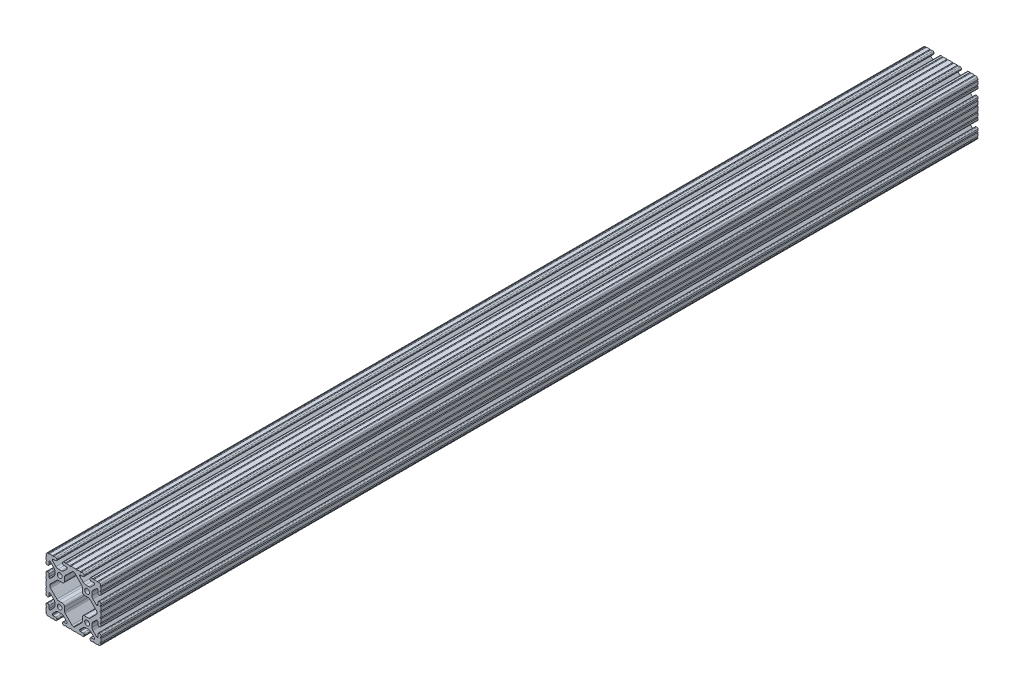
SolidWorks part; units mm, degrees
ref_plane "Front Plane" through (0, 0, 0) normal (0, 0, 1) x (1, 0, 0)
ref_plane "Top Plane" through (0, 0, 0) normal (0, 1, 0) x (1, 0, 0)
ref_plane "Right Plane" through (0, 0, 0) normal (1, 0, 0) x (0, 0, -1)
sketch "Sketch1" plane through (0, 0, 0) normal (0, 0, 1) x (1, 0, 0)
  line L0 (0, 38.1) -> (0, -38.1) construction
  line L1 (-38.1, -38.1) -> (38.1, -38.1) construction
  line L2 (-38.1, -38.1) -> (-38.1, 38.1) construction
  line L3 (-38.1, 38.1) -> (38.1, 38.1) construction
  line L4 (38.1, -38.1) -> (38.1, 38.1) construction
  line L5 (0, 38.1) -> (0, -38.1) construction
  line L6 (-38.1, 0) -> (38.1, 0) construction
  line L7 (-19.05, 19.05) -> (19.05, 19.05) construction
  line L8 (-19.05, 19.05) -> (-19.05, -19.05) construction
  line L9 (-19.05, -19.05) -> (19.05, -19.05) construction
  line L10 (19.05, 19.05) -> (19.05, -19.05) construction
  line L11 (-23.114, 38.1) -> (-23.114, -38.1) construction
  line L12 (-23.114, -38.1) -> (-14.986, 38.1) construction
  line L13 (-14.986, 38.1) -> (-14.986, -38.1) construction
  circle A0 centre (19.05, 19.05) radius 3.3274
  point P0 (0, 0)
  point P9 (0, 0)
  point P12 (-19.05, 0)
  line B0 (-11.3637, -22.8433) -> (-2.0515, -32.1555)
  line B1 (-12.2936, -15.4686) -> (-12.2936, -20.5983)
  line B2 (-20.769, -12.2936) -> (-15.4686, -12.2936)
  line B3 (-31.9021, -2.4756) -> (-23.0141, -11.3637)
  line B4 (-23.0141, 11.3637) -> (-31.9021, 2.4756)
  line B5 (-15.4686, 12.2936) -> (-20.769, 12.2936)
  line B6 (-12.2936, 20.5983) -> (-12.2936, 15.4686)
  line B7 (-2.0515, 32.1555) -> (-11.3637, 22.8433)
  line B8 (11.3637, 22.8433) -> (2.0515, 32.1555)
  line B9 (12.2936, 15.4686) -> (12.2936, 20.5983)
  line B10 (20.769, 12.2936) -> (15.4686, 12.2936)
  line B11 (31.9021, 2.4756) -> (23.0141, 11.3637)
  line B12 (23.0141, -11.3637) -> (31.9021, -2.4756)
  line B13 (15.4686, -12.2936) -> (20.769, -12.2936)
  line B14 (12.2936, -20.5983) -> (12.2936, -15.4686)
  line B15 (2.0515, -32.1555) -> (11.3637, -22.8433)
  line B16 (-4.7773, 38.1) -> (-9.6053, 38.1)
  line B17 (-11.1289, 38.1) -> (-13.4112, 38.1)
  line B18 (-14.986, 36.5252) -> (-14.986, 35.6108)
  line B19 (-13.4112, 34.036) -> (-9.652, 34.036)
  line B20 (-8.763, 33.147) -> (-8.763, 32.4935)
  line B21 (-9.0234, 31.8649) -> (-13.6907, 27.1976)
  line B22 (-17.0493, 25.8064) -> (-21.0507, 25.8064)
  line B23 (-24.4093, 27.1976) -> (-29.1002, 31.8885)
  line B24 (-29.337, 32.7207) -> (-29.337, 33.147)
  line B25 (-28.448, 34.036) -> (-24.6888, 34.036)
  line B26 (-23.114, 35.6108) -> (-23.114, 36.5252)
  line B27 (-24.6888, 38.1) -> (-27.0772, 38.1)
  line B28 (-28.6011, 38.1) -> (-33.4288, 38.1)
  line B29 (-38.1, 33.373) -> (-38.1, 28.5453)
  line B30 (-38.1, 27.0238) -> (-38.1, 24.6302)
  line B31 (-36.5252, 23.0554) -> (-35.6108, 23.0554)
  line B32 (-34.036, 24.6302) -> (-34.036, 28.448)
  line B33 (-33.147, 29.337) -> (-32.6643, 29.337)
  line B34 (-32.0357, 29.0766) -> (-27.1976, 24.2385)
  line B35 (-25.8064, 20.8799) -> (-25.8064, 17.2201)
  line B36 (-27.1976, 13.8615) -> (-31.9489, 9.1101)
  line B37 (-32.7869, 8.763) -> (-33.0603, 8.763)
  line B38 (-34.036, 9.7387) -> (-34.036, 13.4698)
  line B39 (-35.6108, 15.0446) -> (-36.5252, 15.0446)
  line B40 (-38.1, 13.4698) -> (-38.1, 11.075)
  line B41 (-38.1, 9.552) -> (-38.1, 4.7238)
  line B42 (-38.1, 3.2007) -> (-38.1, -3.2007)
  line B43 (-38.1, -4.7238) -> (-38.1, -9.552)
  line B44 (-38.1, -11.075) -> (-38.1, -13.4698)
  line B45 (-36.5252, -15.0446) -> (-35.6108, -15.0446)
  line B46 (-34.036, -13.4698) -> (-34.036, -9.7387)
  line B47 (-33.0603, -8.763) -> (-32.7869, -8.763)
  line B48 (-31.9489, -9.1101) -> (-27.1976, -13.8615)
  line B49 (-25.8064, -17.2201) -> (-25.8064, -20.8799)
  line B50 (-27.1976, -24.2385) -> (-32.0357, -29.0766)
  line B51 (-32.6643, -29.337) -> (-33.147, -29.337)
  line B52 (-34.036, -28.448) -> (-34.036, -24.6302)
  line B53 (-35.6108, -23.0554) -> (-36.5252, -23.0554)
  line B54 (-38.1, -24.6302) -> (-38.1, -27.0238)
  line B55 (-38.1, -28.5453) -> (-38.1, -33.373)
  line B56 (-33.4288, -38.1) -> (-28.6011, -38.1)
  line B57 (-27.0772, -38.1) -> (-24.6888, -38.1)
  line B58 (-23.114, -36.5252) -> (-23.114, -35.6108)
  line B59 (-24.6888, -34.036) -> (-28.448, -34.036)
  line B60 (-29.337, -33.147) -> (-29.337, -32.7207)
  line B61 (-29.1002, -31.8885) -> (-24.4093, -27.1976)
  line B62 (-21.0507, -25.8064) -> (-17.0493, -25.8064)
  line B63 (-13.6907, -27.1976) -> (-9.0234, -31.8649)
  line B64 (-8.763, -32.4935) -> (-8.763, -33.147)
  line B65 (-9.652, -34.036) -> (-13.4112, -34.036)
  line B66 (-14.986, -35.6108) -> (-14.986, -36.5252)
  line B67 (-13.4112, -38.1) -> (-11.1289, -38.1)
  line B68 (-9.6053, -38.1) -> (-4.7773, -38.1)
  line B69 (-3.2537, -38.1) -> (3.2537, -38.1)
  line B70 (4.7773, -38.1) -> (9.6053, -38.1)
  line B71 (11.1289, -38.1) -> (13.4112, -38.1)
  line B72 (14.986, -36.5252) -> (14.986, -35.6108)
  line B73 (13.4112, -34.036) -> (9.652, -34.036)
  line B74 (8.763, -33.147) -> (8.763, -32.4935)
  line B75 (9.0234, -31.8649) -> (13.6907, -27.1976)
  line B76 (17.0493, -25.8064) -> (21.0507, -25.8064)
  line B77 (24.4093, -27.1976) -> (29.1002, -31.8885)
  line B78 (29.337, -32.7207) -> (29.337, -33.147)
  line B79 (28.448, -34.036) -> (24.6888, -34.036)
  line B80 (23.114, -35.6108) -> (23.114, -36.5252)
  line B81 (24.6888, -38.1) -> (27.0772, -38.1)
  line B82 (28.6011, -38.1) -> (33.4288, -38.1)
  line B83 (38.1, -33.373) -> (38.1, -28.5453)
  line B84 (38.1, -27.0238) -> (38.1, -24.6302)
  line B85 (36.5252, -23.0554) -> (35.6108, -23.0554)
  line B86 (34.036, -24.6302) -> (34.036, -28.448)
  line B87 (33.147, -29.337) -> (32.6643, -29.337)
  line B88 (32.0357, -29.0766) -> (27.1976, -24.2385)
  line B89 (25.8064, -20.8799) -> (25.8064, -17.2201)
  line B90 (27.1976, -13.8615) -> (31.9489, -9.1101)
  line B91 (32.7869, -8.763) -> (33.0603, -8.763)
  line B92 (34.036, -9.7387) -> (34.036, -13.4698)
  line B93 (35.6108, -15.0446) -> (36.5252, -15.0446)
  line B94 (38.1, -13.4698) -> (38.1, -11.075)
  line B95 (38.1, -9.552) -> (38.1, -4.7238)
  line B96 (38.1, -3.2007) -> (38.1, 3.2007)
  line B97 (38.1, 4.7238) -> (38.1, 9.552)
  line B98 (38.1, 11.075) -> (38.1, 13.4698)
  line B99 (36.5252, 15.0446) -> (35.6108, 15.0446)
  line B100 (34.036, 13.4698) -> (34.036, 9.7387)
  line B101 (33.0603, 8.763) -> (32.7869, 8.763)
  line B102 (31.9489, 9.1101) -> (27.1976, 13.8615)
  line B103 (25.8064, 17.2201) -> (25.8064, 20.8799)
  line B104 (27.1976, 24.2385) -> (32.0357, 29.0766)
  line B105 (32.6643, 29.337) -> (33.147, 29.337)
  line B106 (34.036, 28.448) -> (34.036, 24.6302)
  line B107 (35.6108, 23.0554) -> (36.5252, 23.0554)
  line B108 (38.1, 24.6302) -> (38.1, 27.0238)
  line B109 (38.1, 28.5453) -> (38.1, 33.373)
  line B110 (33.4288, 38.1) -> (28.6011, 38.1)
  line B111 (27.0772, 38.1) -> (24.6888, 38.1)
  line B112 (23.114, 36.5252) -> (23.114, 35.6108)
  line B113 (24.6888, 34.036) -> (28.448, 34.036)
  line B114 (29.337, 33.147) -> (29.337, 32.7207)
  line B115 (29.1002, 31.8885) -> (24.4093, 27.1976)
  line B116 (21.0507, 25.8064) -> (17.0493, 25.8064)
  line B117 (13.6907, 27.1976) -> (9.0234, 31.8649)
  line B118 (8.763, 32.4935) -> (8.763, 33.147)
  line B119 (9.652, 34.036) -> (13.4112, 34.036)
  line B120 (14.986, 35.6108) -> (14.986, 36.5252)
  line B121 (13.4112, 38.1) -> (11.1289, 38.1)
  line B122 (9.6053, 38.1) -> (4.7773, 38.1)
  line B123 (3.2537, 38.1) -> (-3.2537, 38.1)
  circle B124 centre (-19.05, 19.05) radius 3.3274
  circle B125 centre (-19.05, -19.05) radius 3.3274
  circle B126 centre (19.05, -19.05) radius 3.3274
  circle B127 centre (19.05, 19.05) radius 3.3274
  arc B128 (0, -33.011) -> (2.0515, -32.1555) centre (-0.0139, -30.09) ccw
  arc B129 (-2.0515, -32.1555) -> (0, -33.011) centre (0.0139, -30.09) ccw
  arc B130 (-12.2936, -20.5983) -> (-11.3637, -22.8433) centre (-9.1186, -20.5983) ccw
  arc B131 (-12.2936, -15.4686) -> (-15.4686, -12.2936) centre (-15.4686, -15.4686) ccw
  arc B132 (-23.0141, -11.3637) -> (-20.769, -12.2936) centre (-20.769, -9.1186) ccw
  arc B133 (-32.7287, 0) -> (-31.9021, -2.4756) centre (-29.8367, -0.4102) ccw
  arc B134 (-31.9021, 2.4756) -> (-32.7287, 0) centre (-29.8367, 0.4102) ccw
  arc B135 (-20.769, 12.2936) -> (-23.0141, 11.3637) centre (-20.769, 9.1186) ccw
  arc B136 (-15.4686, 12.2936) -> (-12.2936, 15.4686) centre (-15.4686, 15.4686) ccw
  arc B137 (-11.3637, 22.8433) -> (-12.2936, 20.5983) centre (-9.1186, 20.5983) ccw
  arc B138 (0, 33.011) -> (-2.0515, 32.1555) centre (0.0139, 30.09) ccw
  arc B139 (2.0515, 32.1555) -> (0, 33.011) centre (-0.0139, 30.09) ccw
  arc B140 (12.2936, 20.5983) -> (11.3637, 22.8433) centre (9.1186, 20.5983) ccw
  arc B141 (12.2936, 15.4686) -> (15.4686, 12.2936) centre (15.4686, 15.4686) ccw
  arc B142 (23.0141, 11.3637) -> (20.769, 12.2936) centre (20.769, 9.1186) ccw
  arc B143 (32.7287, 0) -> (31.9021, 2.4756) centre (29.8367, 0.4102) ccw
  arc B144 (31.9021, -2.4756) -> (32.7287, 0) centre (29.8367, -0.4102) ccw
  arc B145 (20.769, -12.2936) -> (23.0141, -11.3637) centre (20.769, -9.1186) ccw
  arc B146 (15.4686, -12.2936) -> (12.2936, -15.4686) centre (15.4686, -15.4686) ccw
  arc B147 (11.3637, -22.8433) -> (12.2936, -20.5983) centre (9.1186, -20.5983) ccw
  arc B148 (-4.7773, 38.1) -> (-3.2537, 38.1) centre (-4.0155, 38.0824) ccw
  arc B149 (-11.1289, 38.1) -> (-9.6053, 38.1) centre (-10.3671, 38.0824) ccw
  arc B150 (-13.4112, 38.1) -> (-14.986, 36.5252) centre (-13.4112, 36.5252) ccw
  arc B151 (-14.986, 35.6108) -> (-13.4112, 34.036) centre (-13.4112, 35.6108) ccw
  arc B152 (-8.763, 33.147) -> (-9.652, 34.036) centre (-9.652, 33.147) ccw
  arc B153 (-9.0234, 31.8649) -> (-8.763, 32.4935) centre (-9.652, 32.4935) ccw
  arc B154 (-17.0493, 25.8064) -> (-13.6907, 27.1976) centre (-17.0493, 30.5562) ccw
  arc B155 (-24.4093, 27.1976) -> (-21.0507, 25.8064) centre (-21.0507, 30.5562) ccw
  arc B156 (-29.337, 32.7207) -> (-29.1002, 31.8885) centre (-28.4716, 32.5172) ccw
  arc B157 (-28.448, 34.036) -> (-29.337, 33.147) centre (-28.448, 33.147) ccw
  arc B158 (-24.6888, 34.036) -> (-23.114, 35.6108) centre (-24.6888, 35.6108) ccw
  arc B159 (-23.114, 36.5252) -> (-24.6888, 38.1) centre (-24.6888, 36.5252) ccw
  arc B160 (-28.6011, 38.1) -> (-27.0772, 38.1) centre (-27.8392, 38.0824) ccw
  arc B161 (-34.9527, 38.1) -> (-33.4288, 38.1) centre (-34.1907, 38.0824) ccw
  arc B162 (-34.9527, 38.1) -> (-37.0861, 37.1826) centre (-34.8521, 34.9266) ccw
  arc B163 (-37.0861, 37.1826) -> (-38.1, 34.8455) centre (-34.925, 34.8566) ccw
  arc B164 (-38.1, 33.373) -> (-38.1, 34.8455) centre (-37.9035, 34.1092) ccw
  arc B165 (-38.1, 27.0238) -> (-38.1, 28.5453) centre (-37.9035, 27.7845) ccw
  arc B166 (-38.1, 24.6302) -> (-36.5252, 23.0554) centre (-36.5252, 24.6302) ccw
  arc B167 (-35.6108, 23.0554) -> (-34.036, 24.6302) centre (-35.6108, 24.6302) ccw
  arc B168 (-33.147, 29.337) -> (-34.036, 28.448) centre (-33.147, 28.448) ccw
  arc B169 (-32.0357, 29.0766) -> (-32.6643, 29.337) centre (-32.6643, 28.448) ccw
  arc B170 (-25.8064, 20.8799) -> (-27.1976, 24.2385) centre (-30.5562, 20.8799) ccw
  arc B171 (-27.1976, 13.8615) -> (-25.8064, 17.2201) centre (-30.5562, 17.2201) ccw
  arc B172 (-32.7869, 8.763) -> (-31.9489, 9.1101) centre (-32.7869, 9.9481) ccw
  arc B173 (-34.036, 9.7387) -> (-33.0603, 8.763) centre (-33.0603, 9.7387) ccw
  arc B174 (-34.036, 13.4698) -> (-35.6108, 15.0446) centre (-35.6108, 13.4698) ccw
  arc B175 (-36.5252, 15.0446) -> (-38.1, 13.4698) centre (-36.5252, 13.4698) ccw
  arc B176 (-38.1, 9.552) -> (-38.1, 11.075) centre (-37.9035, 10.3135) ccw
  arc B177 (-38.1, 3.2007) -> (-38.1, 4.7238) centre (-37.9035, 3.9622) ccw
  arc B178 (-38.1, -4.7238) -> (-38.1, -3.2007) centre (-37.9035, -3.9622) ccw
  arc B179 (-38.1, -11.075) -> (-38.1, -9.552) centre (-37.9035, -10.3135) ccw
  arc B180 (-38.1, -13.4698) -> (-36.5252, -15.0446) centre (-36.5252, -13.4698) ccw
  arc B181 (-35.6108, -15.0446) -> (-34.036, -13.4698) centre (-35.6108, -13.4698) ccw
  arc B182 (-33.0603, -8.763) -> (-34.036, -9.7387) centre (-33.0603, -9.7387) ccw
  arc B183 (-31.9489, -9.1101) -> (-32.7869, -8.763) centre (-32.7869, -9.9481) ccw
  arc B184 (-25.8064, -17.2201) -> (-27.1976, -13.8615) centre (-30.5562, -17.2201) ccw
  arc B185 (-27.1976, -24.2385) -> (-25.8064, -20.8799) centre (-30.5562, -20.8799) ccw
  arc B186 (-32.6643, -29.337) -> (-32.0357, -29.0766) centre (-32.6643, -28.448) ccw
  arc B187 (-34.036, -28.448) -> (-33.147, -29.337) centre (-33.147, -28.448) ccw
  arc B188 (-34.036, -24.6302) -> (-35.6108, -23.0554) centre (-35.6108, -24.6302) ccw
  arc B189 (-36.5252, -23.0554) -> (-38.1, -24.6302) centre (-36.5252, -24.6302) ccw
  arc B190 (-38.1, -28.5453) -> (-38.1, -27.0238) centre (-37.9035, -27.7845) ccw
  arc B191 (-38.1, -34.8455) -> (-38.1, -33.373) centre (-37.9035, -34.1092) ccw
  arc B192 (-38.1, -34.8455) -> (-37.0861, -37.1826) centre (-34.925, -34.8566) ccw
  arc B193 (-37.0861, -37.1826) -> (-34.9527, -38.1) centre (-34.8521, -34.9266) ccw
  arc B194 (-33.4288, -38.1) -> (-34.9527, -38.1) centre (-34.1907, -38.0824) ccw
  arc B195 (-27.0772, -38.1) -> (-28.6011, -38.1) centre (-27.8392, -38.0824) ccw
  arc B196 (-24.6888, -38.1) -> (-23.114, -36.5252) centre (-24.6888, -36.5252) ccw
  arc B197 (-23.114, -35.6108) -> (-24.6888, -34.036) centre (-24.6888, -35.6108) ccw
  arc B198 (-29.337, -33.147) -> (-28.448, -34.036) centre (-28.448, -33.147) ccw
  arc B199 (-29.1002, -31.8885) -> (-29.337, -32.7207) centre (-28.4716, -32.5172) ccw
  arc B200 (-21.0507, -25.8064) -> (-24.4093, -27.1976) centre (-21.0507, -30.5562) ccw
  arc B201 (-13.6907, -27.1976) -> (-17.0493, -25.8064) centre (-17.0493, -30.5562) ccw
  arc B202 (-8.763, -32.4935) -> (-9.0234, -31.8649) centre (-9.652, -32.4935) ccw
  arc B203 (-9.652, -34.036) -> (-8.763, -33.147) centre (-9.652, -33.147) ccw
  arc B204 (-13.4112, -34.036) -> (-14.986, -35.6108) centre (-13.4112, -35.6108) ccw
  arc B205 (-14.986, -36.5252) -> (-13.4112, -38.1) centre (-13.4112, -36.5252) ccw
  arc B206 (-9.6053, -38.1) -> (-11.1289, -38.1) centre (-10.3671, -38.0824) ccw
  arc B207 (-3.2537, -38.1) -> (-4.7773, -38.1) centre (-4.0155, -38.0824) ccw
  arc B208 (4.7773, -38.1) -> (3.2537, -38.1) centre (4.0155, -38.0824) ccw
  arc B209 (11.1289, -38.1) -> (9.6053, -38.1) centre (10.3671, -38.0824) ccw
  arc B210 (13.4112, -38.1) -> (14.986, -36.5252) centre (13.4112, -36.5252) ccw
  arc B211 (14.986, -35.6108) -> (13.4112, -34.036) centre (13.4112, -35.6108) ccw
  arc B212 (8.763, -33.147) -> (9.652, -34.036) centre (9.652, -33.147) ccw
  arc B213 (9.0234, -31.8649) -> (8.763, -32.4935) centre (9.652, -32.4935) ccw
  arc B214 (17.0493, -25.8064) -> (13.6907, -27.1976) centre (17.0493, -30.5562) ccw
  arc B215 (24.4093, -27.1976) -> (21.0507, -25.8064) centre (21.0507, -30.5562) ccw
  arc B216 (29.337, -32.7207) -> (29.1002, -31.8885) centre (28.4716, -32.5172) ccw
  arc B217 (28.448, -34.036) -> (29.337, -33.147) centre (28.448, -33.147) ccw
  arc B218 (24.6888, -34.036) -> (23.114, -35.6108) centre (24.6888, -35.6108) ccw
  arc B219 (23.114, -36.5252) -> (24.6888, -38.1) centre (24.6888, -36.5252) ccw
  arc B220 (28.6011, -38.1) -> (27.0772, -38.1) centre (27.8392, -38.0824) ccw
  arc B221 (34.9527, -38.1) -> (33.4288, -38.1) centre (34.1907, -38.0824) ccw
  arc B222 (34.9527, -38.1) -> (37.0861, -37.1826) centre (34.8521, -34.9266) ccw
  arc B223 (37.0861, -37.1826) -> (38.1, -34.8455) centre (34.925, -34.8566) ccw
  arc B224 (38.1, -33.373) -> (38.1, -34.8455) centre (37.9035, -34.1092) ccw
  arc B225 (38.1, -27.0238) -> (38.1, -28.5453) centre (37.9035, -27.7845) ccw
  arc B226 (38.1, -24.6302) -> (36.5252, -23.0554) centre (36.5252, -24.6302) ccw
  arc B227 (35.6108, -23.0554) -> (34.036, -24.6302) centre (35.6108, -24.6302) ccw
  arc B228 (33.147, -29.337) -> (34.036, -28.448) centre (33.147, -28.448) ccw
  arc B229 (32.0357, -29.0766) -> (32.6643, -29.337) centre (32.6643, -28.448) ccw
  arc B230 (25.8064, -20.8799) -> (27.1976, -24.2385) centre (30.5562, -20.8799) ccw
  arc B231 (27.1976, -13.8615) -> (25.8064, -17.2201) centre (30.5562, -17.2201) ccw
  arc B232 (32.7869, -8.763) -> (31.9489, -9.1101) centre (32.7869, -9.9481) ccw
  arc B233 (34.036, -9.7387) -> (33.0603, -8.763) centre (33.0603, -9.7387) ccw
  arc B234 (34.036, -13.4698) -> (35.6108, -15.0446) centre (35.6108, -13.4698) ccw
  arc B235 (36.5252, -15.0446) -> (38.1, -13.4698) centre (36.5252, -13.4698) ccw
  arc B236 (38.1, -9.552) -> (38.1, -11.075) centre (37.9035, -10.3135) ccw
  arc B237 (38.1, -3.2007) -> (38.1, -4.7238) centre (37.9035, -3.9622) ccw
  arc B238 (38.1, 4.7238) -> (38.1, 3.2007) centre (37.9035, 3.9622) ccw
  arc B239 (38.1, 11.075) -> (38.1, 9.552) centre (37.9035, 10.3135) ccw
  arc B240 (38.1, 13.4698) -> (36.5252, 15.0446) centre (36.5252, 13.4698) ccw
  arc B241 (35.6108, 15.0446) -> (34.036, 13.4698) centre (35.6108, 13.4698) ccw
  arc B242 (33.0603, 8.763) -> (34.036, 9.7387) centre (33.0603, 9.7387) ccw
  arc B243 (31.9489, 9.1101) -> (32.7869, 8.763) centre (32.7869, 9.9481) ccw
  arc B244 (25.8064, 17.2201) -> (27.1976, 13.8615) centre (30.5562, 17.2201) ccw
  arc B245 (27.1976, 24.2385) -> (25.8064, 20.8799) centre (30.5562, 20.8799) ccw
  arc B246 (32.6643, 29.337) -> (32.0357, 29.0766) centre (32.6643, 28.448) ccw
  arc B247 (34.036, 28.448) -> (33.147, 29.337) centre (33.147, 28.448) ccw
  arc B248 (34.036, 24.6302) -> (35.6108, 23.0554) centre (35.6108, 24.6302) ccw
  arc B249 (36.5252, 23.0554) -> (38.1, 24.6302) centre (36.5252, 24.6302) ccw
  arc B250 (38.1, 28.5453) -> (38.1, 27.0238) centre (37.9035, 27.7845) ccw
  arc B251 (38.1, 34.8455) -> (38.1, 33.373) centre (37.9035, 34.1092) ccw
  arc B252 (38.1, 34.8455) -> (37.0861, 37.1826) centre (34.925, 34.8566) ccw
  arc B253 (37.0861, 37.1826) -> (34.9527, 38.1) centre (34.8521, 34.9266) ccw
  arc B254 (33.4288, 38.1) -> (34.9527, 38.1) centre (34.1907, 38.0824) ccw
  arc B255 (27.0772, 38.1) -> (28.6011, 38.1) centre (27.8392, 38.0824) ccw
  arc B256 (24.6888, 38.1) -> (23.114, 36.5252) centre (24.6888, 36.5252) ccw
  arc B257 (23.114, 35.6108) -> (24.6888, 34.036) centre (24.6888, 35.6108) ccw
  arc B258 (29.337, 33.147) -> (28.448, 34.036) centre (28.448, 33.147) ccw
  arc B259 (29.1002, 31.8885) -> (29.337, 32.7207) centre (28.4716, 32.5172) ccw
  arc B260 (21.0507, 25.8064) -> (24.4093, 27.1976) centre (21.0507, 30.5562) ccw
  arc B261 (13.6907, 27.1976) -> (17.0493, 25.8064) centre (17.0493, 30.5562) ccw
  arc B262 (8.763, 32.4935) -> (9.0234, 31.8649) centre (9.652, 32.4935) ccw
  arc B263 (9.652, 34.036) -> (8.763, 33.147) centre (9.652, 33.147) ccw
  arc B264 (13.4112, 34.036) -> (14.986, 35.6108) centre (13.4112, 35.6108) ccw
  arc B265 (14.986, 36.5252) -> (13.4112, 38.1) centre (13.4112, 36.5252) ccw
  arc B266 (9.6053, 38.1) -> (11.1289, 38.1) centre (10.3671, 38.0824) ccw
  arc B267 (3.2537, 38.1) -> (4.7773, 38.1) centre (4.0155, 38.0824) ccw
  dimension "Center Hole Diameter" = 6.6548
  dimension "Rail Width" = 76.2
  dimension "Rail Height" = 76.2
  dimension "T-Slot Width" = 8.128
sketch_block_instance "Block1-1"
sketch_block "Block1"
sketch "Sketch2" plane through (0, 0, 0) normal (1, 0, 0) x (0, 0, -1)
  line L0 (-609.6, 0) -> (609.6, 0) construction
  line L1 (-609.6, 38.1) -> (-609.6, -38.1) construction
  line L2 (-609.6, -38.1) -> (609.6, -38.1) construction
  line L3 (609.6, -38.1) -> (609.6, 38.1) construction
  line L4 (-508, 0) -> (-508, 38.1) construction
  line L5 (-508, 38.1) -> (508, 38.1) construction
  line L6 (508, 38.1) -> (508, 0) construction
  point P5 (508, 0)
  point P10 (-508, 0)
  dimension "D1" = 101.6
  dimension "Length" = 1219.2
  dimension "D2" = 101.6
sketch "Sketch3" plane through (0, 0, 0) normal (0, 0, 1) x (1, 0, 0)
  line L0 (-11.3637, -22.8433) -> (-2.0515, -32.1555) construction
  line L1 (-12.2936, -15.4686) -> (-12.2936, -20.5983) construction
  line L2 (-20.769, -12.2936) -> (-15.4686, -12.2936) construction
  line L3 (-31.9021, -2.4756) -> (-23.0141, -11.3637) construction
  line L4 (-23.0141, 11.3637) -> (-31.9021, 2.4756) construction
  line L5 (-15.4686, 12.2936) -> (-20.769, 12.2936) construction
  line L6 (-12.2936, 20.5983) -> (-12.2936, 15.4686) construction
  line L7 (-2.0515, 32.1555) -> (-11.3637, 22.8433) construction
  line L8 (11.3637, 22.8433) -> (2.0515, 32.1555) construction
  line L9 (12.2936, 15.4686) -> (12.2936, 20.5983) construction
  line L10 (20.769, 12.2936) -> (15.4686, 12.2936) construction
  line L11 (31.9021, 2.4756) -> (23.0141, 11.3637) construction
  line L12 (23.0141, -11.3637) -> (31.9021, -2.4756) construction
  line L13 (15.4686, -12.2936) -> (20.769, -12.2936) construction
  line L14 (12.2936, -20.5983) -> (12.2936, -15.4686) construction
  line L15 (2.0515, -32.1555) -> (11.3637, -22.8433) construction
  line L16 (34.036, 28.448) -> (34.036, 24.6302) construction
  line L17 (35.6108, 23.0554) -> (36.5252, 23.0554) construction
  line L18 (38.1, 24.6302) -> (38.1, 27.0238) construction
  line L19 (38.1, 28.5453) -> (38.1, 33.373) construction
  line L20 (33.4288, 38.1) -> (28.6011, 38.1) construction
  line L21 (27.0772, 38.1) -> (24.6888, 38.1) construction
  line L22 (23.114, 36.5252) -> (23.114, 35.6108) construction
  line L23 (24.6888, 34.036) -> (28.448, 34.036) construction
  line L24 (29.337, 33.147) -> (29.337, 32.7207) construction
  line L25 (29.1002, 31.8885) -> (24.4093, 27.1976) construction
  line L26 (21.0507, 25.8064) -> (17.0493, 25.8064) construction
  line L27 (13.6907, 27.1976) -> (9.0234, 31.8649) construction
  line L28 (8.763, 32.4935) -> (8.763, 33.147) construction
  line L29 (9.652, 34.036) -> (13.4112, 34.036) construction
  line L30 (14.986, 35.6108) -> (14.986, 36.5252) construction
  line L31 (13.4112, 38.1) -> (11.1289, 38.1) construction
  line L32 (9.6053, 38.1) -> (4.7773, 38.1) construction
  line L33 (3.2537, 38.1) -> (-3.2537, 38.1) construction
  line L34 (-4.7773, 38.1) -> (-9.6053, 38.1) construction
  line L35 (-11.1289, 38.1) -> (-13.4112, 38.1) construction
  line L36 (-14.986, 36.5252) -> (-14.986, 35.6108) construction
  line L37 (-13.4112, 34.036) -> (-9.652, 34.036) construction
  line L38 (-8.763, 33.147) -> (-8.763, 32.4935) construction
  line L39 (-9.0234, 31.8649) -> (-13.6907, 27.1976) construction
  line L40 (-17.0493, 25.8064) -> (-21.0507, 25.8064) construction
  line L41 (-24.4093, 27.1976) -> (-29.1002, 31.8885) construction
  line L42 (-29.337, 32.7207) -> (-29.337, 33.147) construction
  line L43 (-28.448, 34.036) -> (-24.6888, 34.036) construction
  line L44 (-23.114, 35.6108) -> (-23.114, 36.5252) construction
  line L45 (-24.6888, 38.1) -> (-27.0772, 38.1) construction
  line L46 (-28.6011, 38.1) -> (-33.4288, 38.1) construction
  line L47 (-38.1, 33.373) -> (-38.1, 28.5453) construction
  line L48 (-38.1, 27.0238) -> (-38.1, 24.6302) construction
  line L49 (-36.5252, 23.0554) -> (-35.6108, 23.0554) construction
  line L50 (-34.036, 24.6302) -> (-34.036, 28.448) construction
  line L51 (-33.147, 29.337) -> (-32.6643, 29.337) construction
  line L52 (-32.0357, 29.0766) -> (-27.1976, 24.2385) construction
  line L53 (-25.8064, 20.8799) -> (-25.8064, 17.2201) construction
  line L54 (-27.1976, 13.8615) -> (-31.9489, 9.1101) construction
  line L55 (-32.7869, 8.763) -> (-33.0603, 8.763) construction
  line L56 (-34.036, 9.7387) -> (-34.036, 13.4698) construction
  line L57 (-35.6108, 15.0446) -> (-36.5252, 15.0446) construction
  line L58 (-38.1, 13.4698) -> (-38.1, 11.075) construction
  line L59 (-38.1, 9.552) -> (-38.1, 4.7238) construction
  line L60 (-38.1, 3.2007) -> (-38.1, -3.2007) construction
  line L61 (-38.1, -4.7238) -> (-38.1, -9.552) construction
  line L62 (-38.1, -11.075) -> (-38.1, -13.4698) construction
  line L63 (-36.5252, -15.0446) -> (-35.6108, -15.0446) construction
  line L64 (-34.036, -13.4698) -> (-34.036, -9.7387) construction
  line L65 (-33.0603, -8.763) -> (-32.7869, -8.763) construction
  line L66 (-31.9489, -9.1101) -> (-27.1976, -13.8615) construction
  line L67 (-25.8064, -17.2201) -> (-25.8064, -20.8799) construction
  line L68 (-27.1976, -24.2385) -> (-32.0357, -29.0766) construction
  line L69 (-32.6643, -29.337) -> (-33.147, -29.337) construction
  line L70 (-34.036, -28.448) -> (-34.036, -24.6302) construction
  line L71 (-35.6108, -23.0554) -> (-36.5252, -23.0554) construction
  line L72 (-38.1, -24.6302) -> (-38.1, -27.0238) construction
  line L73 (-38.1, -28.5453) -> (-38.1, -33.373) construction
  line L74 (-33.4288, -38.1) -> (-28.6011, -38.1) construction
  line L75 (-27.0772, -38.1) -> (-24.6888, -38.1) construction
  line L76 (-23.114, -36.5252) -> (-23.114, -35.6108) construction
  line L77 (-24.6888, -34.036) -> (-28.448, -34.036) construction
  line L78 (-29.337, -33.147) -> (-29.337, -32.7207) construction
  line L79 (-29.1002, -31.8885) -> (-24.4093, -27.1976) construction
  line L80 (-21.0507, -25.8064) -> (-17.0493, -25.8064) construction
  line L81 (-13.6907, -27.1976) -> (-9.0234, -31.8649) construction
  line L82 (-8.763, -32.4935) -> (-8.763, -33.147) construction
  line L83 (-9.652, -34.036) -> (-13.4112, -34.036) construction
  line L84 (-14.986, -35.6108) -> (-14.986, -36.5252) construction
  line L85 (-13.4112, -38.1) -> (-11.1289, -38.1) construction
  line L86 (-9.6053, -38.1) -> (-4.7773, -38.1) construction
  line L87 (-3.2537, -38.1) -> (3.2537, -38.1) construction
  line L88 (4.7773, -38.1) -> (9.6053, -38.1) construction
  line L89 (11.1289, -38.1) -> (13.4112, -38.1) construction
  line L90 (14.986, -36.5252) -> (14.986, -35.6108) construction
  line L91 (13.4112, -34.036) -> (9.652, -34.036) construction
  line L92 (8.763, -33.147) -> (8.763, -32.4935) construction
  line L93 (9.0234, -31.8649) -> (13.6907, -27.1976) construction
  line L94 (17.0493, -25.8064) -> (21.0507, -25.8064) construction
  line L95 (24.4093, -27.1976) -> (29.1002, -31.8885) construction
  line L96 (29.337, -32.7207) -> (29.337, -33.147) construction
  line L97 (28.448, -34.036) -> (24.6888, -34.036) construction
  line L98 (23.114, -35.6108) -> (23.114, -36.5252) construction
  line L99 (24.6888, -38.1) -> (27.0772, -38.1) construction
  line L100 (28.6011, -38.1) -> (33.4288, -38.1) construction
  line L101 (38.1, -33.373) -> (38.1, -28.5453) construction
  line L102 (38.1, -27.0238) -> (38.1, -24.6302) construction
  line L103 (36.5252, -23.0554) -> (35.6108, -23.0554) construction
  line L104 (34.036, -24.6302) -> (34.036, -28.448) construction
  line L105 (33.147, -29.337) -> (32.6643, -29.337) construction
  line L106 (32.0357, -29.0766) -> (27.1976, -24.2385) construction
  line L107 (25.8064, -20.8799) -> (25.8064, -17.2201) construction
  line L108 (27.1976, -13.8615) -> (31.9489, -9.1101) construction
  line L109 (32.7869, -8.763) -> (33.0603, -8.763) construction
  line L110 (34.036, -9.7387) -> (34.036, -13.4698) construction
  line L111 (35.6108, -15.0446) -> (36.5252, -15.0446) construction
  line L112 (38.1, -13.4698) -> (38.1, -11.075) construction
  line L113 (38.1, -9.552) -> (38.1, -4.7238) construction
  line L114 (38.1, -3.2007) -> (38.1, 3.2007) construction
  line L115 (38.1, 4.7238) -> (38.1, 9.552) construction
  line L116 (38.1, 11.075) -> (38.1, 13.4698) construction
  line L117 (36.5252, 15.0446) -> (35.6108, 15.0446) construction
  line L118 (34.036, 13.4698) -> (34.036, 9.7387) construction
  line L119 (33.0603, 8.763) -> (32.7869, 8.763) construction
  line L120 (31.9489, 9.1101) -> (27.1976, 13.8615) construction
  line L121 (25.8064, 17.2201) -> (25.8064, 20.8799) construction
  line L122 (27.1976, 24.2385) -> (32.0357, 29.0766) construction
  line L123 (32.6643, 29.337) -> (33.147, 29.337) construction
  line L124 (-11.3637, -22.8433) -> (-2.0515, -32.1555)
  line L125 (-12.2936, -15.4686) -> (-12.2936, -20.5983)
  line L126 (-20.769, -12.2936) -> (-15.4686, -12.2936)
  line L127 (-31.9021, -2.4756) -> (-23.0141, -11.3637)
  line L128 (-23.0141, 11.3637) -> (-31.9021, 2.4756)
  line L129 (-15.4686, 12.2936) -> (-20.769, 12.2936)
  line L130 (-12.2936, 20.5983) -> (-12.2936, 15.4686)
  line L131 (-2.0515, 32.1555) -> (-11.3637, 22.8433)
  line L132 (11.3637, 22.8433) -> (2.0515, 32.1555)
  line L133 (12.2936, 15.4686) -> (12.2936, 20.5983)
  line L134 (20.769, 12.2936) -> (15.4686, 12.2936)
  line L135 (31.9021, 2.4756) -> (23.0141, 11.3637)
  line L136 (23.0141, -11.3637) -> (31.9021, -2.4756)
  line L137 (15.4686, -12.2936) -> (20.769, -12.2936)
  line L138 (12.2936, -20.5983) -> (12.2936, -15.4686)
  line L139 (2.0515, -32.1555) -> (11.3637, -22.8433)
  line L140 (34.036, 28.448) -> (34.036, 24.6302)
  line L141 (35.6108, 23.0554) -> (36.5252, 23.0554)
  line L142 (38.1, 24.6302) -> (38.1, 27.0238)
  line L143 (38.1, 28.5453) -> (38.1, 33.373)
  line L144 (33.4288, 38.1) -> (28.6011, 38.1)
  line L145 (27.0772, 38.1) -> (24.6888, 38.1)
  line L146 (23.114, 36.5252) -> (23.114, 35.6108)
  line L147 (24.6888, 34.036) -> (28.448, 34.036)
  line L148 (29.337, 33.147) -> (29.337, 32.7207)
  line L149 (29.1002, 31.8885) -> (24.4093, 27.1976)
  line L150 (21.0507, 25.8064) -> (17.0493, 25.8064)
  line L151 (13.6907, 27.1976) -> (9.0234, 31.8649)
  line L152 (8.763, 32.4935) -> (8.763, 33.147)
  line L153 (9.652, 34.036) -> (13.4112, 34.036)
  line L154 (14.986, 35.6108) -> (14.986, 36.5252)
  line L155 (13.4112, 38.1) -> (11.1289, 38.1)
  line L156 (9.6053, 38.1) -> (4.7773, 38.1)
  line L157 (3.2537, 38.1) -> (-3.2537, 38.1)
  line L158 (-4.7773, 38.1) -> (-9.6053, 38.1)
  line L159 (-11.1289, 38.1) -> (-13.4112, 38.1)
  line L160 (-14.986, 36.5252) -> (-14.986, 35.6108)
  line L161 (-13.4112, 34.036) -> (-9.652, 34.036)
  line L162 (-8.763, 33.147) -> (-8.763, 32.4935)
  line L163 (-9.0234, 31.8649) -> (-13.6907, 27.1976)
  line L164 (-17.0493, 25.8064) -> (-21.0507, 25.8064)
  line L165 (-24.4093, 27.1976) -> (-29.1002, 31.8885)
  line L166 (-29.337, 32.7207) -> (-29.337, 33.147)
  line L167 (-28.448, 34.036) -> (-24.6888, 34.036)
  line L168 (-23.114, 35.6108) -> (-23.114, 36.5252)
  line L169 (-24.6888, 38.1) -> (-27.0772, 38.1)
  line L170 (-28.6011, 38.1) -> (-33.4288, 38.1)
  line L171 (-38.1, 33.373) -> (-38.1, 28.5453)
  line L172 (-38.1, 27.0238) -> (-38.1, 24.6302)
  line L173 (-36.5252, 23.0554) -> (-35.6108, 23.0554)
  line L174 (-34.036, 24.6302) -> (-34.036, 28.448)
  line L175 (-33.147, 29.337) -> (-32.6643, 29.337)
  line L176 (-32.0357, 29.0766) -> (-27.1976, 24.2385)
  line L177 (-25.8064, 20.8799) -> (-25.8064, 17.2201)
  line L178 (-27.1976, 13.8615) -> (-31.9489, 9.1101)
  line L179 (-32.7869, 8.763) -> (-33.0603, 8.763)
  line L180 (-34.036, 9.7387) -> (-34.036, 13.4698)
  line L181 (-35.6108, 15.0446) -> (-36.5252, 15.0446)
  line L182 (-38.1, 13.4698) -> (-38.1, 11.075)
  line L183 (-38.1, 9.552) -> (-38.1, 4.7238)
  line L184 (-38.1, 3.2007) -> (-38.1, -3.2007)
  line L185 (-38.1, -4.7238) -> (-38.1, -9.552)
  line L186 (-38.1, -11.075) -> (-38.1, -13.4698)
  line L187 (-36.5252, -15.0446) -> (-35.6108, -15.0446)
  line L188 (-34.036, -13.4698) -> (-34.036, -9.7387)
  line L189 (-33.0603, -8.763) -> (-32.7869, -8.763)
  line L190 (-31.9489, -9.1101) -> (-27.1976, -13.8615)
  line L191 (-25.8064, -17.2201) -> (-25.8064, -20.8799)
  line L192 (-27.1976, -24.2385) -> (-32.0357, -29.0766)
  line L193 (-32.6643, -29.337) -> (-33.147, -29.337)
  line L194 (-34.036, -28.448) -> (-34.036, -24.6302)
  line L195 (-35.6108, -23.0554) -> (-36.5252, -23.0554)
  line L196 (-38.1, -24.6302) -> (-38.1, -27.0238)
  line L197 (-38.1, -28.5453) -> (-38.1, -33.373)
  line L198 (-33.4288, -38.1) -> (-28.6011, -38.1)
  line L199 (-27.0772, -38.1) -> (-24.6888, -38.1)
  line L200 (-23.114, -36.5252) -> (-23.114, -35.6108)
  line L201 (-24.6888, -34.036) -> (-28.448, -34.036)
  line L202 (-29.337, -33.147) -> (-29.337, -32.7207)
  line L203 (-29.1002, -31.8885) -> (-24.4093, -27.1976)
  line L204 (-21.0507, -25.8064) -> (-17.0493, -25.8064)
  line L205 (-13.6907, -27.1976) -> (-9.0234, -31.8649)
  line L206 (-8.763, -32.4935) -> (-8.763, -33.147)
  line L207 (-9.652, -34.036) -> (-13.4112, -34.036)
  line L208 (-14.986, -35.6108) -> (-14.986, -36.5252)
  line L209 (-13.4112, -38.1) -> (-11.1289, -38.1)
  line L210 (-9.6053, -38.1) -> (-4.7773, -38.1)
  line L211 (-3.2537, -38.1) -> (3.2537, -38.1)
  line L212 (4.7773, -38.1) -> (9.6053, -38.1)
  line L213 (11.1289, -38.1) -> (13.4112, -38.1)
  line L214 (14.986, -36.5252) -> (14.986, -35.6108)
  line L215 (13.4112, -34.036) -> (9.652, -34.036)
  line L216 (8.763, -33.147) -> (8.763, -32.4935)
  line L217 (9.0234, -31.8649) -> (13.6907, -27.1976)
  line L218 (17.0493, -25.8064) -> (21.0507, -25.8064)
  line L219 (24.4093, -27.1976) -> (29.1002, -31.8885)
  line L220 (29.337, -32.7207) -> (29.337, -33.147)
  line L221 (28.448, -34.036) -> (24.6888, -34.036)
  line L222 (23.114, -35.6108) -> (23.114, -36.5252)
  line L223 (24.6888, -38.1) -> (27.0772, -38.1)
  line L224 (28.6011, -38.1) -> (33.4288, -38.1)
  line L225 (38.1, -33.373) -> (38.1, -28.5453)
  line L226 (38.1, -27.0238) -> (38.1, -24.6302)
  line L227 (36.5252, -23.0554) -> (35.6108, -23.0554)
  line L228 (34.036, -24.6302) -> (34.036, -28.448)
  line L229 (33.147, -29.337) -> (32.6643, -29.337)
  line L230 (32.0357, -29.0766) -> (27.1976, -24.2385)
  line L231 (25.8064, -20.8799) -> (25.8064, -17.2201)
  line L232 (27.1976, -13.8615) -> (31.9489, -9.1101)
  line L233 (32.7869, -8.763) -> (33.0603, -8.763)
  line L234 (34.036, -9.7387) -> (34.036, -13.4698)
  line L235 (35.6108, -15.0446) -> (36.5252, -15.0446)
  line L236 (38.1, -13.4698) -> (38.1, -11.075)
  line L237 (38.1, -9.552) -> (38.1, -4.7238)
  line L238 (38.1, -3.2007) -> (38.1, 3.2007)
  line L239 (38.1, 4.7238) -> (38.1, 9.552)
  line L240 (38.1, 11.075) -> (38.1, 13.4698)
  line L241 (36.5252, 15.0446) -> (35.6108, 15.0446)
  line L242 (34.036, 13.4698) -> (34.036, 9.7387)
  line L243 (33.0603, 8.763) -> (32.7869, 8.763)
  line L244 (31.9489, 9.1101) -> (27.1976, 13.8615)
  line L245 (25.8064, 17.2201) -> (25.8064, 20.8799)
  line L246 (27.1976, 24.2385) -> (32.0357, 29.0766)
  line L247 (32.6643, 29.337) -> (33.147, 29.337)
  arc A0 (-2.0515, -32.1555) -> (0, -33.011) centre (0.0139, -30.09) ccw construction
  circle A1 centre (19.05, 19.05) radius 3.3274
  circle A2 centre (19.05, 19.05) radius 3.3274
  arc A3 (-12.2936, -20.5983) -> (-11.3637, -22.8433) centre (-9.1186, -20.5983) ccw construction
  arc A4 (-12.2936, -15.4686) -> (-15.4686, -12.2936) centre (-15.4686, -15.4686) ccw construction
  arc A5 (-23.0141, -11.3637) -> (-20.769, -12.2936) centre (-20.769, -9.1186) ccw construction
  arc A6 (-32.7287, 0) -> (-31.9021, -2.4756) centre (-29.8367, -0.4102) ccw construction
  arc A7 (-31.9021, 2.4756) -> (-32.7287, 0) centre (-29.8367, 0.4102) ccw construction
  arc A8 (-20.769, 12.2936) -> (-23.0141, 11.3637) centre (-20.769, 9.1186) ccw construction
  arc A9 (-15.4686, 12.2936) -> (-12.2936, 15.4686) centre (-15.4686, 15.4686) ccw construction
  arc A10 (-11.3637, 22.8433) -> (-12.2936, 20.5983) centre (-9.1186, 20.5983) ccw construction
  arc A11 (0, 33.011) -> (-2.0515, 32.1555) centre (0.0139, 30.09) ccw construction
  arc A12 (2.0515, 32.1555) -> (0, 33.011) centre (-0.0139, 30.09) ccw construction
  arc A13 (12.2936, 20.5983) -> (11.3637, 22.8433) centre (9.1186, 20.5983) ccw construction
  arc A14 (12.2936, 15.4686) -> (15.4686, 12.2936) centre (15.4686, 15.4686) ccw construction
  arc A15 (23.0141, 11.3637) -> (20.769, 12.2936) centre (20.769, 9.1186) ccw construction
  arc A16 (32.7287, 0) -> (31.9021, 2.4756) centre (29.8367, 0.4102) ccw construction
  arc A17 (31.9021, -2.4756) -> (32.7287, 0) centre (29.8367, -0.4102) ccw construction
  arc A18 (20.769, -12.2936) -> (23.0141, -11.3637) centre (20.769, -9.1186) ccw construction
  arc A19 (15.4686, -12.2936) -> (12.2936, -15.4686) centre (15.4686, -15.4686) ccw construction
  arc A20 (11.3637, -22.8433) -> (12.2936, -20.5983) centre (9.1186, -20.5983) ccw construction
  arc A21 (0, -33.011) -> (2.0515, -32.1555) centre (-0.0139, -30.09) ccw construction
  circle A22 centre (-19.05, 19.05) radius 3.3274 construction
  circle A23 centre (19.05, -19.05) radius 3.3274 construction
  circle A24 centre (-19.05, -19.05) radius 3.3274 construction
  circle A25 centre (19.05, 19.05) radius 3.3274 construction
  arc A26 (34.036, 24.6302) -> (35.6108, 23.0554) centre (35.6108, 24.6302) ccw construction
  arc A27 (36.5252, 23.0554) -> (38.1, 24.6302) centre (36.5252, 24.6302) ccw construction
  arc A28 (38.1, 28.5453) -> (38.1, 27.0238) centre (37.9035, 27.7845) ccw construction
  arc A29 (38.1, 34.8455) -> (38.1, 33.373) centre (37.9035, 34.1092) ccw construction
  arc A30 (38.1, 34.8455) -> (37.0861, 37.1826) centre (34.925, 34.8566) ccw construction
  arc A31 (37.0861, 37.1826) -> (34.9527, 38.1) centre (34.8521, 34.9266) ccw construction
  arc A32 (33.4288, 38.1) -> (34.9527, 38.1) centre (34.1907, 38.0824) ccw construction
  arc A33 (27.0772, 38.1) -> (28.6011, 38.1) centre (27.8392, 38.0824) ccw construction
  arc A34 (24.6888, 38.1) -> (23.114, 36.5252) centre (24.6888, 36.5252) ccw construction
  arc A35 (23.114, 35.6108) -> (24.6888, 34.036) centre (24.6888, 35.6108) ccw construction
  arc A36 (29.337, 33.147) -> (28.448, 34.036) centre (28.448, 33.147) ccw construction
  arc A37 (29.1002, 31.8885) -> (29.337, 32.7207) centre (28.4716, 32.5172) ccw construction
  arc A38 (21.0507, 25.8064) -> (24.4093, 27.1976) centre (21.0507, 30.5562) ccw construction
  arc A39 (13.6907, 27.1976) -> (17.0493, 25.8064) centre (17.0493, 30.5562) ccw construction
  arc A40 (8.763, 32.4935) -> (9.0234, 31.8649) centre (9.652, 32.4935) ccw construction
  arc A41 (9.652, 34.036) -> (8.763, 33.147) centre (9.652, 33.147) ccw construction
  arc A42 (13.4112, 34.036) -> (14.986, 35.6108) centre (13.4112, 35.6108) ccw construction
  arc A43 (14.986, 36.5252) -> (13.4112, 38.1) centre (13.4112, 36.5252) ccw construction
  arc A44 (9.6053, 38.1) -> (11.1289, 38.1) centre (10.3671, 38.0824) ccw construction
  arc A45 (3.2537, 38.1) -> (4.7773, 38.1) centre (4.0155, 38.0824) ccw construction
  arc A46 (-4.7773, 38.1) -> (-3.2537, 38.1) centre (-4.0155, 38.0824) ccw construction
  arc A47 (-11.1289, 38.1) -> (-9.6053, 38.1) centre (-10.3671, 38.0824) ccw construction
  arc A48 (-13.4112, 38.1) -> (-14.986, 36.5252) centre (-13.4112, 36.5252) ccw construction
  arc A49 (-14.986, 35.6108) -> (-13.4112, 34.036) centre (-13.4112, 35.6108) ccw construction
  arc A50 (-8.763, 33.147) -> (-9.652, 34.036) centre (-9.652, 33.147) ccw construction
  arc A51 (-9.0234, 31.8649) -> (-8.763, 32.4935) centre (-9.652, 32.4935) ccw construction
  arc A52 (-17.0493, 25.8064) -> (-13.6907, 27.1976) centre (-17.0493, 30.5562) ccw construction
  arc A53 (-24.4093, 27.1976) -> (-21.0507, 25.8064) centre (-21.0507, 30.5562) ccw construction
  arc A54 (-29.337, 32.7207) -> (-29.1002, 31.8885) centre (-28.4716, 32.5172) ccw construction
  arc A55 (-28.448, 34.036) -> (-29.337, 33.147) centre (-28.448, 33.147) ccw construction
  arc A56 (-24.6888, 34.036) -> (-23.114, 35.6108) centre (-24.6888, 35.6108) ccw construction
  arc A57 (-23.114, 36.5252) -> (-24.6888, 38.1) centre (-24.6888, 36.5252) ccw construction
  arc A58 (-28.6011, 38.1) -> (-27.0772, 38.1) centre (-27.8392, 38.0824) ccw construction
  arc A59 (-34.9527, 38.1) -> (-33.4288, 38.1) centre (-34.1907, 38.0824) ccw construction
  arc A60 (-34.9527, 38.1) -> (-37.0861, 37.1826) centre (-34.8521, 34.9266) ccw construction
  arc A61 (-37.0861, 37.1826) -> (-38.1, 34.8455) centre (-34.925, 34.8566) ccw construction
  arc A62 (-38.1, 33.373) -> (-38.1, 34.8455) centre (-37.9035, 34.1092) ccw construction
  arc A63 (-38.1, 27.0238) -> (-38.1, 28.5453) centre (-37.9035, 27.7845) ccw construction
  arc A64 (-38.1, 24.6302) -> (-36.5252, 23.0554) centre (-36.5252, 24.6302) ccw construction
  arc A65 (-35.6108, 23.0554) -> (-34.036, 24.6302) centre (-35.6108, 24.6302) ccw construction
  arc A66 (-33.147, 29.337) -> (-34.036, 28.448) centre (-33.147, 28.448) ccw construction
  arc A67 (-32.0357, 29.0766) -> (-32.6643, 29.337) centre (-32.6643, 28.448) ccw construction
  arc A68 (-25.8064, 20.8799) -> (-27.1976, 24.2385) centre (-30.5562, 20.8799) ccw construction
  arc A69 (-27.1976, 13.8615) -> (-25.8064, 17.2201) centre (-30.5562, 17.2201) ccw construction
  arc A70 (-32.7869, 8.763) -> (-31.9489, 9.1101) centre (-32.7869, 9.9481) ccw construction
  arc A71 (-34.036, 9.7387) -> (-33.0603, 8.763) centre (-33.0603, 9.7387) ccw construction
  arc A72 (-34.036, 13.4698) -> (-35.6108, 15.0446) centre (-35.6108, 13.4698) ccw construction
  arc A73 (-36.5252, 15.0446) -> (-38.1, 13.4698) centre (-36.5252, 13.4698) ccw construction
  arc A74 (-38.1, 9.552) -> (-38.1, 11.075) centre (-37.9035, 10.3135) ccw construction
  arc A75 (-38.1, 3.2007) -> (-38.1, 4.7238) centre (-37.9035, 3.9622) ccw construction
  arc A76 (-38.1, -4.7238) -> (-38.1, -3.2007) centre (-37.9035, -3.9622) ccw construction
  arc A77 (-38.1, -11.075) -> (-38.1, -9.552) centre (-37.9035, -10.3135) ccw construction
  arc A78 (-38.1, -13.4698) -> (-36.5252, -15.0446) centre (-36.5252, -13.4698) ccw construction
  arc A79 (-35.6108, -15.0446) -> (-34.036, -13.4698) centre (-35.6108, -13.4698) ccw construction
  arc A80 (-33.0603, -8.763) -> (-34.036, -9.7387) centre (-33.0603, -9.7387) ccw construction
  arc A81 (-31.9489, -9.1101) -> (-32.7869, -8.763) centre (-32.7869, -9.9481) ccw construction
  arc A82 (-25.8064, -17.2201) -> (-27.1976, -13.8615) centre (-30.5562, -17.2201) ccw construction
  arc A83 (-27.1976, -24.2385) -> (-25.8064, -20.8799) centre (-30.5562, -20.8799) ccw construction
  arc A84 (-32.6643, -29.337) -> (-32.0357, -29.0766) centre (-32.6643, -28.448) ccw construction
  arc A85 (-34.036, -28.448) -> (-33.147, -29.337) centre (-33.147, -28.448) ccw construction
  arc A86 (-34.036, -24.6302) -> (-35.6108, -23.0554) centre (-35.6108, -24.6302) ccw construction
  arc A87 (-36.5252, -23.0554) -> (-38.1, -24.6302) centre (-36.5252, -24.6302) ccw construction
  arc A88 (-38.1, -28.5453) -> (-38.1, -27.0238) centre (-37.9035, -27.7845) ccw construction
  arc A89 (-38.1, -34.8455) -> (-38.1, -33.373) centre (-37.9035, -34.1092) ccw construction
  arc A90 (-38.1, -34.8455) -> (-37.0861, -37.1826) centre (-34.925, -34.8566) ccw construction
  arc A91 (-37.0861, -37.1826) -> (-34.9527, -38.1) centre (-34.8521, -34.9266) ccw construction
  arc A92 (-33.4288, -38.1) -> (-34.9527, -38.1) centre (-34.1907, -38.0824) ccw construction
  arc A93 (-27.0772, -38.1) -> (-28.6011, -38.1) centre (-27.8392, -38.0824) ccw construction
  arc A94 (-24.6888, -38.1) -> (-23.114, -36.5252) centre (-24.6888, -36.5252) ccw construction
  arc A95 (-23.114, -35.6108) -> (-24.6888, -34.036) centre (-24.6888, -35.6108) ccw construction
  arc A96 (-29.337, -33.147) -> (-28.448, -34.036) centre (-28.448, -33.147) ccw construction
  arc A97 (-29.1002, -31.8885) -> (-29.337, -32.7207) centre (-28.4716, -32.5172) ccw construction
  arc A98 (-21.0507, -25.8064) -> (-24.4093, -27.1976) centre (-21.0507, -30.5562) ccw construction
  arc A99 (-13.6907, -27.1976) -> (-17.0493, -25.8064) centre (-17.0493, -30.5562) ccw construction
  arc A100 (-8.763, -32.4935) -> (-9.0234, -31.8649) centre (-9.652, -32.4935) ccw construction
  arc A101 (-9.652, -34.036) -> (-8.763, -33.147) centre (-9.652, -33.147) ccw construction
  arc A102 (-13.4112, -34.036) -> (-14.986, -35.6108) centre (-13.4112, -35.6108) ccw construction
  arc A103 (-14.986, -36.5252) -> (-13.4112, -38.1) centre (-13.4112, -36.5252) ccw construction
  arc A104 (-9.6053, -38.1) -> (-11.1289, -38.1) centre (-10.3671, -38.0824) ccw construction
  arc A105 (-3.2537, -38.1) -> (-4.7773, -38.1) centre (-4.0155, -38.0824) ccw construction
  arc A106 (4.7773, -38.1) -> (3.2537, -38.1) centre (4.0155, -38.0824) ccw construction
  arc A107 (11.1289, -38.1) -> (9.6053, -38.1) centre (10.3671, -38.0824) ccw construction
  arc A108 (13.4112, -38.1) -> (14.986, -36.5252) centre (13.4112, -36.5252) ccw construction
  arc A109 (14.986, -35.6108) -> (13.4112, -34.036) centre (13.4112, -35.6108) ccw construction
  arc A110 (8.763, -33.147) -> (9.652, -34.036) centre (9.652, -33.147) ccw construction
  arc A111 (9.0234, -31.8649) -> (8.763, -32.4935) centre (9.652, -32.4935) ccw construction
  arc A112 (17.0493, -25.8064) -> (13.6907, -27.1976) centre (17.0493, -30.5562) ccw construction
  arc A113 (24.4093, -27.1976) -> (21.0507, -25.8064) centre (21.0507, -30.5562) ccw construction
  arc A114 (29.337, -32.7207) -> (29.1002, -31.8885) centre (28.4716, -32.5172) ccw construction
  arc A115 (28.448, -34.036) -> (29.337, -33.147) centre (28.448, -33.147) ccw construction
  arc A116 (24.6888, -34.036) -> (23.114, -35.6108) centre (24.6888, -35.6108) ccw construction
  arc A117 (23.114, -36.5252) -> (24.6888, -38.1) centre (24.6888, -36.5252) ccw construction
  arc A118 (28.6011, -38.1) -> (27.0772, -38.1) centre (27.8392, -38.0824) ccw construction
  arc A119 (34.9527, -38.1) -> (33.4288, -38.1) centre (34.1907, -38.0824) ccw construction
  arc A120 (34.9527, -38.1) -> (37.0861, -37.1826) centre (34.8521, -34.9266) ccw construction
  arc A121 (37.0861, -37.1826) -> (38.1, -34.8455) centre (34.925, -34.8566) ccw construction
  arc A122 (38.1, -33.373) -> (38.1, -34.8455) centre (37.9035, -34.1092) ccw construction
  arc A123 (38.1, -27.0238) -> (38.1, -28.5453) centre (37.9035, -27.7845) ccw construction
  arc A124 (38.1, -24.6302) -> (36.5252, -23.0554) centre (36.5252, -24.6302) ccw construction
  arc A125 (35.6108, -23.0554) -> (34.036, -24.6302) centre (35.6108, -24.6302) ccw construction
  arc A126 (33.147, -29.337) -> (34.036, -28.448) centre (33.147, -28.448) ccw construction
  arc A127 (32.0357, -29.0766) -> (32.6643, -29.337) centre (32.6643, -28.448) ccw construction
  arc A128 (25.8064, -20.8799) -> (27.1976, -24.2385) centre (30.5562, -20.8799) ccw construction
  arc A129 (27.1976, -13.8615) -> (25.8064, -17.2201) centre (30.5562, -17.2201) ccw construction
  arc A130 (32.7869, -8.763) -> (31.9489, -9.1101) centre (32.7869, -9.9481) ccw construction
  arc A131 (34.036, -9.7387) -> (33.0603, -8.763) centre (33.0603, -9.7387) ccw construction
  arc A132 (34.036, -13.4698) -> (35.6108, -15.0446) centre (35.6108, -13.4698) ccw construction
  arc A133 (36.5252, -15.0446) -> (38.1, -13.4698) centre (36.5252, -13.4698) ccw construction
  arc A134 (38.1, -9.552) -> (38.1, -11.075) centre (37.9035, -10.3135) ccw construction
  arc A135 (38.1, -3.2007) -> (38.1, -4.7238) centre (37.9035, -3.9622) ccw construction
  arc A136 (38.1, 4.7238) -> (38.1, 3.2007) centre (37.9035, 3.9622) ccw construction
  arc A137 (38.1, 11.075) -> (38.1, 9.552) centre (37.9035, 10.3135) ccw construction
  arc A138 (38.1, 13.4698) -> (36.5252, 15.0446) centre (36.5252, 13.4698) ccw construction
  arc A139 (35.6108, 15.0446) -> (34.036, 13.4698) centre (35.6108, 13.4698) ccw construction
  arc A140 (33.0603, 8.763) -> (34.036, 9.7387) centre (33.0603, 9.7387) ccw construction
  arc A141 (31.9489, 9.1101) -> (32.7869, 8.763) centre (32.7869, 9.9481) ccw construction
  arc A142 (25.8064, 17.2201) -> (27.1976, 13.8615) centre (30.5562, 17.2201) ccw construction
  arc A143 (27.1976, 24.2385) -> (25.8064, 20.8799) centre (30.5562, 20.8799) ccw construction
  arc A144 (32.6643, 29.337) -> (32.0357, 29.0766) centre (32.6643, 28.448) ccw construction
  arc A145 (34.036, 28.448) -> (33.147, 29.337) centre (33.147, 28.448) ccw construction
  arc A146 (-2.0515, -32.1555) -> (0, -33.011) centre (0.0139, -30.09) ccw
  arc A147 (-12.2936, -20.5983) -> (-11.3637, -22.8433) centre (-9.1186, -20.5983) ccw
  arc A148 (-12.2936, -15.4686) -> (-15.4686, -12.2936) centre (-15.4686, -15.4686) ccw
  arc A149 (-23.0141, -11.3637) -> (-20.769, -12.2936) centre (-20.769, -9.1186) ccw
  arc A150 (-32.7287, 0) -> (-31.9021, -2.4756) centre (-29.8367, -0.4102) ccw
  arc A151 (-31.9021, 2.4756) -> (-32.7287, 0) centre (-29.8367, 0.4102) ccw
  arc A152 (-20.769, 12.2936) -> (-23.0141, 11.3637) centre (-20.769, 9.1186) ccw
  arc A153 (-15.4686, 12.2936) -> (-12.2936, 15.4686) centre (-15.4686, 15.4686) ccw
  arc A154 (-11.3637, 22.8433) -> (-12.2936, 20.5983) centre (-9.1186, 20.5983) ccw
  arc A155 (0, 33.011) -> (-2.0515, 32.1555) centre (0.0139, 30.09) ccw
  arc A156 (2.0515, 32.1555) -> (0, 33.011) centre (-0.0139, 30.09) ccw
  arc A157 (12.2936, 20.5983) -> (11.3637, 22.8433) centre (9.1186, 20.5983) ccw
  arc A158 (12.2936, 15.4686) -> (15.4686, 12.2936) centre (15.4686, 15.4686) ccw
  arc A159 (23.0141, 11.3637) -> (20.769, 12.2936) centre (20.769, 9.1186) ccw
  arc A160 (32.7287, 0) -> (31.9021, 2.4756) centre (29.8367, 0.4102) ccw
  arc A161 (31.9021, -2.4756) -> (32.7287, 0) centre (29.8367, -0.4102) ccw
  arc A162 (20.769, -12.2936) -> (23.0141, -11.3637) centre (20.769, -9.1186) ccw
  arc A163 (15.4686, -12.2936) -> (12.2936, -15.4686) centre (15.4686, -15.4686) ccw
  arc A164 (11.3637, -22.8433) -> (12.2936, -20.5983) centre (9.1186, -20.5983) ccw
  arc A165 (0, -33.011) -> (2.0515, -32.1555) centre (-0.0139, -30.09) ccw
  circle A166 centre (-19.05, 19.05) radius 3.3274
  circle A167 centre (19.05, -19.05) radius 3.3274
  circle A168 centre (-19.05, -19.05) radius 3.3274
  circle A169 centre (19.05, 19.05) radius 3.3274
  arc A170 (34.036, 24.6302) -> (35.6108, 23.0554) centre (35.6108, 24.6302) ccw
  arc A171 (36.5252, 23.0554) -> (38.1, 24.6302) centre (36.5252, 24.6302) ccw
  arc A172 (38.1, 28.5453) -> (38.1, 27.0238) centre (37.9035, 27.7845) ccw
  arc A173 (38.1, 34.8455) -> (38.1, 33.373) centre (37.9035, 34.1092) ccw
  arc A174 (38.1, 34.8455) -> (37.0861, 37.1826) centre (34.925, 34.8566) ccw
  arc A175 (37.0861, 37.1826) -> (34.9527, 38.1) centre (34.8521, 34.9266) ccw
  arc A176 (33.4288, 38.1) -> (34.9527, 38.1) centre (34.1907, 38.0824) ccw
  arc A177 (27.0772, 38.1) -> (28.6011, 38.1) centre (27.8392, 38.0824) ccw
  arc A178 (24.6888, 38.1) -> (23.114, 36.5252) centre (24.6888, 36.5252) ccw
  arc A179 (23.114, 35.6108) -> (24.6888, 34.036) centre (24.6888, 35.6108) ccw
  arc A180 (29.337, 33.147) -> (28.448, 34.036) centre (28.448, 33.147) ccw
  arc A181 (29.1002, 31.8885) -> (29.337, 32.7207) centre (28.4716, 32.5172) ccw
  arc A182 (21.0507, 25.8064) -> (24.4093, 27.1976) centre (21.0507, 30.5562) ccw
  arc A183 (13.6907, 27.1976) -> (17.0493, 25.8064) centre (17.0493, 30.5562) ccw
  arc A184 (8.763, 32.4935) -> (9.0234, 31.8649) centre (9.652, 32.4935) ccw
  arc A185 (9.652, 34.036) -> (8.763, 33.147) centre (9.652, 33.147) ccw
  arc A186 (13.4112, 34.036) -> (14.986, 35.6108) centre (13.4112, 35.6108) ccw
  arc A187 (14.986, 36.5252) -> (13.4112, 38.1) centre (13.4112, 36.5252) ccw
  arc A188 (9.6053, 38.1) -> (11.1289, 38.1) centre (10.3671, 38.0824) ccw
  arc A189 (3.2537, 38.1) -> (4.7773, 38.1) centre (4.0155, 38.0824) ccw
  arc A190 (-4.7773, 38.1) -> (-3.2537, 38.1) centre (-4.0155, 38.0824) ccw
  arc A191 (-11.1289, 38.1) -> (-9.6053, 38.1) centre (-10.3671, 38.0824) ccw
  arc A192 (-13.4112, 38.1) -> (-14.986, 36.5252) centre (-13.4112, 36.5252) ccw
  arc A193 (-14.986, 35.6108) -> (-13.4112, 34.036) centre (-13.4112, 35.6108) ccw
  arc A194 (-8.763, 33.147) -> (-9.652, 34.036) centre (-9.652, 33.147) ccw
  arc A195 (-9.0234, 31.8649) -> (-8.763, 32.4935) centre (-9.652, 32.4935) ccw
  arc A196 (-17.0493, 25.8064) -> (-13.6907, 27.1976) centre (-17.0493, 30.5562) ccw
  arc A197 (-24.4093, 27.1976) -> (-21.0507, 25.8064) centre (-21.0507, 30.5562) ccw
  arc A198 (-29.337, 32.7207) -> (-29.1002, 31.8885) centre (-28.4716, 32.5172) ccw
  arc A199 (-28.448, 34.036) -> (-29.337, 33.147) centre (-28.448, 33.147) ccw
  arc A200 (-24.6888, 34.036) -> (-23.114, 35.6108) centre (-24.6888, 35.6108) ccw
  arc A201 (-23.114, 36.5252) -> (-24.6888, 38.1) centre (-24.6888, 36.5252) ccw
  arc A202 (-28.6011, 38.1) -> (-27.0772, 38.1) centre (-27.8392, 38.0824) ccw
  arc A203 (-34.9527, 38.1) -> (-33.4288, 38.1) centre (-34.1907, 38.0824) ccw
  arc A204 (-34.9527, 38.1) -> (-37.0861, 37.1826) centre (-34.8521, 34.9266) ccw
  arc A205 (-37.0861, 37.1826) -> (-38.1, 34.8455) centre (-34.925, 34.8566) ccw
  arc A206 (-38.1, 33.373) -> (-38.1, 34.8455) centre (-37.9035, 34.1092) ccw
  arc A207 (-38.1, 27.0238) -> (-38.1, 28.5453) centre (-37.9035, 27.7845) ccw
  arc A208 (-38.1, 24.6302) -> (-36.5252, 23.0554) centre (-36.5252, 24.6302) ccw
  arc A209 (-35.6108, 23.0554) -> (-34.036, 24.6302) centre (-35.6108, 24.6302) ccw
  arc A210 (-33.147, 29.337) -> (-34.036, 28.448) centre (-33.147, 28.448) ccw
  arc A211 (-32.0357, 29.0766) -> (-32.6643, 29.337) centre (-32.6643, 28.448) ccw
  arc A212 (-25.8064, 20.8799) -> (-27.1976, 24.2385) centre (-30.5562, 20.8799) ccw
  arc A213 (-27.1976, 13.8615) -> (-25.8064, 17.2201) centre (-30.5562, 17.2201) ccw
  arc A214 (-32.7869, 8.763) -> (-31.9489, 9.1101) centre (-32.7869, 9.9481) ccw
  arc A215 (-34.036, 9.7387) -> (-33.0603, 8.763) centre (-33.0603, 9.7387) ccw
  arc A216 (-34.036, 13.4698) -> (-35.6108, 15.0446) centre (-35.6108, 13.4698) ccw
  arc A217 (-36.5252, 15.0446) -> (-38.1, 13.4698) centre (-36.5252, 13.4698) ccw
  arc A218 (-38.1, 9.552) -> (-38.1, 11.075) centre (-37.9035, 10.3135) ccw
  arc A219 (-38.1, 3.2007) -> (-38.1, 4.7238) centre (-37.9035, 3.9622) ccw
  arc A220 (-38.1, -4.7238) -> (-38.1, -3.2007) centre (-37.9035, -3.9622) ccw
  arc A221 (-38.1, -11.075) -> (-38.1, -9.552) centre (-37.9035, -10.3135) ccw
  arc A222 (-38.1, -13.4698) -> (-36.5252, -15.0446) centre (-36.5252, -13.4698) ccw
  arc A223 (-35.6108, -15.0446) -> (-34.036, -13.4698) centre (-35.6108, -13.4698) ccw
  arc A224 (-33.0603, -8.763) -> (-34.036, -9.7387) centre (-33.0603, -9.7387) ccw
  arc A225 (-31.9489, -9.1101) -> (-32.7869, -8.763) centre (-32.7869, -9.9481) ccw
  arc A226 (-25.8064, -17.2201) -> (-27.1976, -13.8615) centre (-30.5562, -17.2201) ccw
  arc A227 (-27.1976, -24.2385) -> (-25.8064, -20.8799) centre (-30.5562, -20.8799) ccw
  arc A228 (-32.6643, -29.337) -> (-32.0357, -29.0766) centre (-32.6643, -28.448) ccw
  arc A229 (-34.036, -28.448) -> (-33.147, -29.337) centre (-33.147, -28.448) ccw
  arc A230 (-34.036, -24.6302) -> (-35.6108, -23.0554) centre (-35.6108, -24.6302) ccw
  arc A231 (-36.5252, -23.0554) -> (-38.1, -24.6302) centre (-36.5252, -24.6302) ccw
  arc A232 (-38.1, -28.5453) -> (-38.1, -27.0238) centre (-37.9035, -27.7845) ccw
  arc A233 (-38.1, -34.8455) -> (-38.1, -33.373) centre (-37.9035, -34.1092) ccw
  arc A234 (-38.1, -34.8455) -> (-37.0861, -37.1826) centre (-34.925, -34.8566) ccw
  arc A235 (-37.0861, -37.1826) -> (-34.9527, -38.1) centre (-34.8521, -34.9266) ccw
  arc A236 (-33.4288, -38.1) -> (-34.9527, -38.1) centre (-34.1907, -38.0824) ccw
  arc A237 (-27.0772, -38.1) -> (-28.6011, -38.1) centre (-27.8392, -38.0824) ccw
  arc A238 (-24.6888, -38.1) -> (-23.114, -36.5252) centre (-24.6888, -36.5252) ccw
  arc A239 (-23.114, -35.6108) -> (-24.6888, -34.036) centre (-24.6888, -35.6108) ccw
  arc A240 (-29.337, -33.147) -> (-28.448, -34.036) centre (-28.448, -33.147) ccw
  arc A241 (-29.1002, -31.8885) -> (-29.337, -32.7207) centre (-28.4716, -32.5172) ccw
  arc A242 (-21.0507, -25.8064) -> (-24.4093, -27.1976) centre (-21.0507, -30.5562) ccw
  arc A243 (-13.6907, -27.1976) -> (-17.0493, -25.8064) centre (-17.0493, -30.5562) ccw
  arc A244 (-8.763, -32.4935) -> (-9.0234, -31.8649) centre (-9.652, -32.4935) ccw
  arc A245 (-9.652, -34.036) -> (-8.763, -33.147) centre (-9.652, -33.147) ccw
  arc A246 (-13.4112, -34.036) -> (-14.986, -35.6108) centre (-13.4112, -35.6108) ccw
  arc A247 (-14.986, -36.5252) -> (-13.4112, -38.1) centre (-13.4112, -36.5252) ccw
  arc A248 (-9.6053, -38.1) -> (-11.1289, -38.1) centre (-10.3671, -38.0824) ccw
  arc A249 (-3.2537, -38.1) -> (-4.7773, -38.1) centre (-4.0155, -38.0824) ccw
  arc A250 (4.7773, -38.1) -> (3.2537, -38.1) centre (4.0155, -38.0824) ccw
  arc A251 (11.1289, -38.1) -> (9.6053, -38.1) centre (10.3671, -38.0824) ccw
  arc A252 (13.4112, -38.1) -> (14.986, -36.5252) centre (13.4112, -36.5252) ccw
  arc A253 (14.986, -35.6108) -> (13.4112, -34.036) centre (13.4112, -35.6108) ccw
  arc A254 (8.763, -33.147) -> (9.652, -34.036) centre (9.652, -33.147) ccw
  arc A255 (9.0234, -31.8649) -> (8.763, -32.4935) centre (9.652, -32.4935) ccw
  arc A256 (17.0493, -25.8064) -> (13.6907, -27.1976) centre (17.0493, -30.5562) ccw
  arc A257 (24.4093, -27.1976) -> (21.0507, -25.8064) centre (21.0507, -30.5562) ccw
  arc A258 (29.337, -32.7207) -> (29.1002, -31.8885) centre (28.4716, -32.5172) ccw
  arc A259 (28.448, -34.036) -> (29.337, -33.147) centre (28.448, -33.147) ccw
  arc A260 (24.6888, -34.036) -> (23.114, -35.6108) centre (24.6888, -35.6108) ccw
  arc A261 (23.114, -36.5252) -> (24.6888, -38.1) centre (24.6888, -36.5252) ccw
  arc A262 (28.6011, -38.1) -> (27.0772, -38.1) centre (27.8392, -38.0824) ccw
  arc A263 (34.9527, -38.1) -> (33.4288, -38.1) centre (34.1907, -38.0824) ccw
  arc A264 (34.9527, -38.1) -> (37.0861, -37.1826) centre (34.8521, -34.9266) ccw
  arc A265 (37.0861, -37.1826) -> (38.1, -34.8455) centre (34.925, -34.8566) ccw
  arc A266 (38.1, -33.373) -> (38.1, -34.8455) centre (37.9035, -34.1092) ccw
  arc A267 (38.1, -27.0238) -> (38.1, -28.5453) centre (37.9035, -27.7845) ccw
  arc A268 (38.1, -24.6302) -> (36.5252, -23.0554) centre (36.5252, -24.6302) ccw
  arc A269 (35.6108, -23.0554) -> (34.036, -24.6302) centre (35.6108, -24.6302) ccw
  arc A270 (33.147, -29.337) -> (34.036, -28.448) centre (33.147, -28.448) ccw
  arc A271 (32.0357, -29.0766) -> (32.6643, -29.337) centre (32.6643, -28.448) ccw
  arc A272 (25.8064, -20.8799) -> (27.1976, -24.2385) centre (30.5562, -20.8799) ccw
  arc A273 (27.1976, -13.8615) -> (25.8064, -17.2201) centre (30.5562, -17.2201) ccw
  arc A274 (32.7869, -8.763) -> (31.9489, -9.1101) centre (32.7869, -9.9481) ccw
  arc A275 (34.036, -9.7387) -> (33.0603, -8.763) centre (33.0603, -9.7387) ccw
  arc A276 (34.036, -13.4698) -> (35.6108, -15.0446) centre (35.6108, -13.4698) ccw
  arc A277 (36.5252, -15.0446) -> (38.1, -13.4698) centre (36.5252, -13.4698) ccw
  arc A278 (38.1, -9.552) -> (38.1, -11.075) centre (37.9035, -10.3135) ccw
  arc A279 (38.1, -3.2007) -> (38.1, -4.7238) centre (37.9035, -3.9622) ccw
  arc A280 (38.1, 4.7238) -> (38.1, 3.2007) centre (37.9035, 3.9622) ccw
  arc A281 (38.1, 11.075) -> (38.1, 9.552) centre (37.9035, 10.3135) ccw
  arc A282 (38.1, 13.4698) -> (36.5252, 15.0446) centre (36.5252, 13.4698) ccw
  arc A283 (35.6108, 15.0446) -> (34.036, 13.4698) centre (35.6108, 13.4698) ccw
  arc A284 (33.0603, 8.763) -> (34.036, 9.7387) centre (33.0603, 9.7387) ccw
  arc A285 (31.9489, 9.1101) -> (32.7869, 8.763) centre (32.7869, 9.9481) ccw
  arc A286 (25.8064, 17.2201) -> (27.1976, 13.8615) centre (30.5562, 17.2201) ccw
  arc A287 (27.1976, 24.2385) -> (25.8064, 20.8799) centre (30.5562, 20.8799) ccw
  arc A288 (32.6643, 29.337) -> (32.0357, 29.0766) centre (32.6643, 28.448) ccw
  arc A289 (34.036, 28.448) -> (33.147, 29.337) centre (33.147, 28.448) ccw
  dimension "D1" = 0
extrude "Boss-Extrude1" add sketch "Sketch3" along normal up to vertex (609.6 mm away) and the other way up to vertex (609.6 mm away) contours A289 L140 A170 L141 A171 L142 A172 L143 A173 A174 A175 A176 L144 A177 L145 A178 L146 A179 L147 A180 L148 A181 L149 A182 L150 A183 L151 A184 L152 A185 L153 A186 L154 A187 L155 A188 L156 A189 L157 A190 L158 A191 L159 A192 L160 A193 L161 A194 L162 A195 L163 region at (34.5376, 29.8386, 0) up to point (0, 0, 609.6) other way up to point (0, 0, -609.6)
